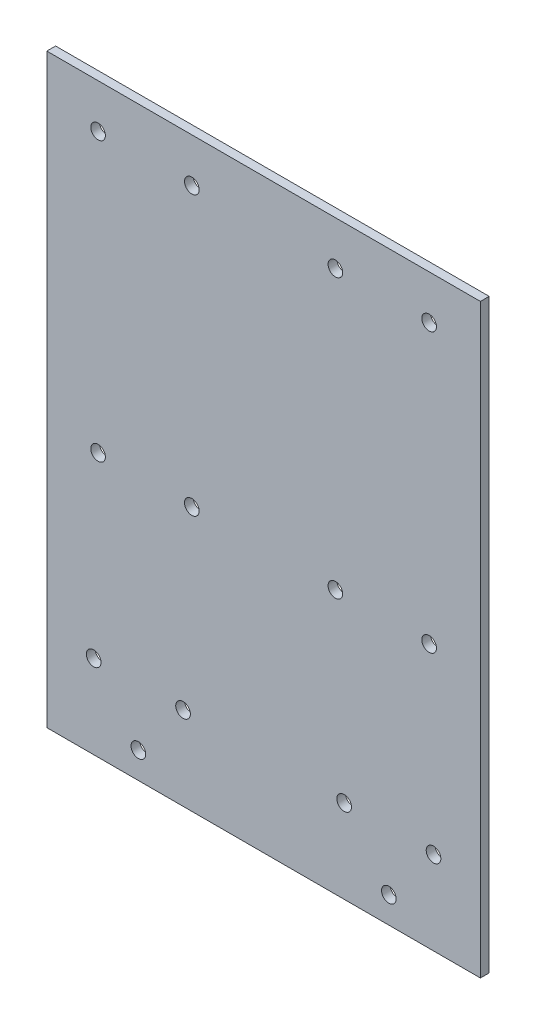
SolidWorks part; units mm, degrees
ref_plane "前视基准面" through (0, 0, 0) normal (0, 0, 1) x (1, 0, 0)
ref_plane "上视基准面" through (0, 0, 0) normal (0, 1, 0) x (1, 0, 0)
ref_plane "右视基准面" through (0, 0, 0) normal (1, 0, 0) x (0, 0, -1)
sketch "草图1" plane through (0, 0, 0) normal (0, 0, 1) x (1, 0, 0)
  line L0 (0, -100) -> (0, 100) construction
  line L1 (74, -100) -> (-74, -100)
  line L2 (74, -100) -> (74, 100)
  line L3 (74, 100) -> (-74, 100)
  line L4 (-74, -100) -> (-74, 100)
  line L5 (74, -100) -> (-74, 100) construction
  line L6 (74, 100) -> (-74, -100) construction
  circle A0 centre (-58, -71.5) radius 2.5
  circle A1 centre (-27.5, -71.5) radius 2.5
  circle A2 centre (-42.75, -91) radius 2.5
  circle A3 centre (42.75, -91) radius 2.5
  circle A4 centre (58, -71.5) radius 2.5
  circle A5 centre (27.5, -71.5) radius 2.5
  point P0 (0, 0)
  dimension "D3" = 5
  dimension "D4" = 5
  dimension "D5" = 5
  dimension "D6" = 9
  dimension "D7" = 16
  dimension "D8" = 30.5
  dimension "D9" = 19.5
  dimension "D10" = 15.25
  dimension "D1" = 148
  dimension "D2" = 200
extrude "凸台-拉伸1" add sketch "草图1" along normal blind 3
sketch "草图2" plane through (0, 0, 3) normal (0, 0, 1) x (1, 0, 0)
  line L0 (-74, 100) -> (-74, -100) construction
  line L1 (-74, -100) -> (74, -100) construction
  line L2 (0, 100) -> (0, -100) construction
  line L3 (74, 100) -> (-74, 100) construction
  circle A0 centre (-56.5, -10) radius 2.5
  circle A1 centre (-24.5, -10) radius 2.5
  circle A2 centre (-56.5, 85) radius 2.5
  circle A3 centre (-24.5, 85) radius 2.5
  circle A4 centre (-56.5, 180) radius 2.5
  circle A5 centre (-24.5, 180) radius 2.5
  circle A6 centre (24.5, 180) radius 2.5
  circle A7 centre (56.5, 180) radius 2.5
  circle A8 centre (24.5, 85) radius 2.5
  circle A9 centre (56.5, 85) radius 2.5
  circle A10 centre (24.5, -10) radius 2.5
  circle A11 centre (56.5, -10) radius 2.5
  dimension "D1" = 5
  dimension "D2" = 5
  dimension "D3" = 32
  dimension "D4" = 17.5
  dimension "D5" = 90
  dimension "D7" = 90
  dimension "D6" = 3
extrude "切除-拉伸1" cut sketch "草图2" against normal blind 3
